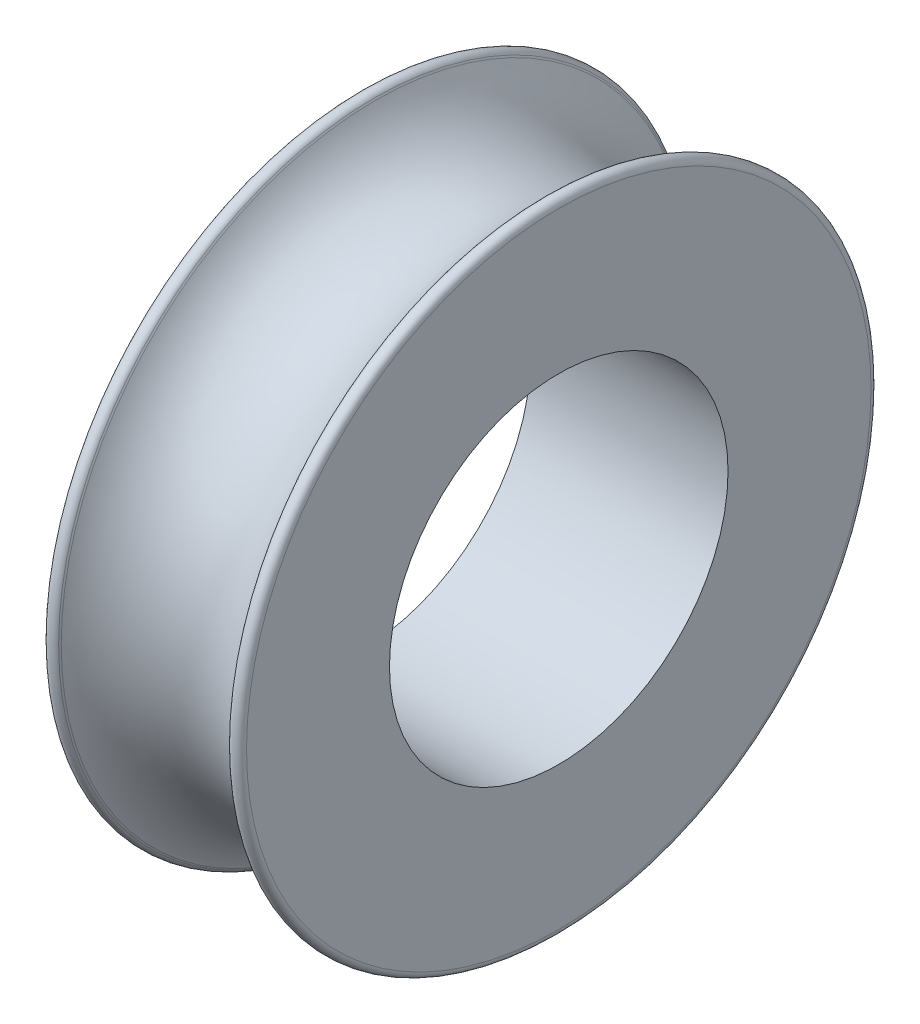
SolidWorks part; units mm, degrees
ref_plane "Front Plane" through (0, 0, 0) normal (0, 0, 1) x (1, 0, 0)
ref_plane "Top Plane" through (0, 0, 0) normal (0, 1, 0) x (1, 0, 0)
ref_plane "Right Plane" through (0, 0, 0) normal (1, 0, 0) x (0, 0, -1)
sketch "Sketch2" plane through (0, 0, 0) normal (0, 0, 1) x (1, 0, 0)
  line L0 (0, 0) -> (7, 0)
  line L1 (7, 0) -> (7, 12)
  line L4 (0, 12) -> (0, 0)
  line L5 (0, 12) -> (0.5, 11.134)
  line L7 (6.5, 11.134) -> (7, 12)
  arc A0 (0.5, 11.134) -> (6.5, 11.134) centre (3.5, 12.6434) ccw
  dimension "D1" = 7
  dimension "D2" = 12
  dimension "D3" = 30
revolve "Revolve1" add sketch "Sketch2" angle 360 about L0
fillet "Fillet1" radius 0.25 2 edges at (7, 0, 12) (0, 0, 12)
sketch "Sketch3" plane through (0, 0, 0) normal (-1, 0, 0) x (0, 0, 1)
  circle A0 centre (0, 0) radius 6
  dimension "D1" = 12
extrude "Cut-Extrude1" cut sketch "Sketch3" against normal up to next
